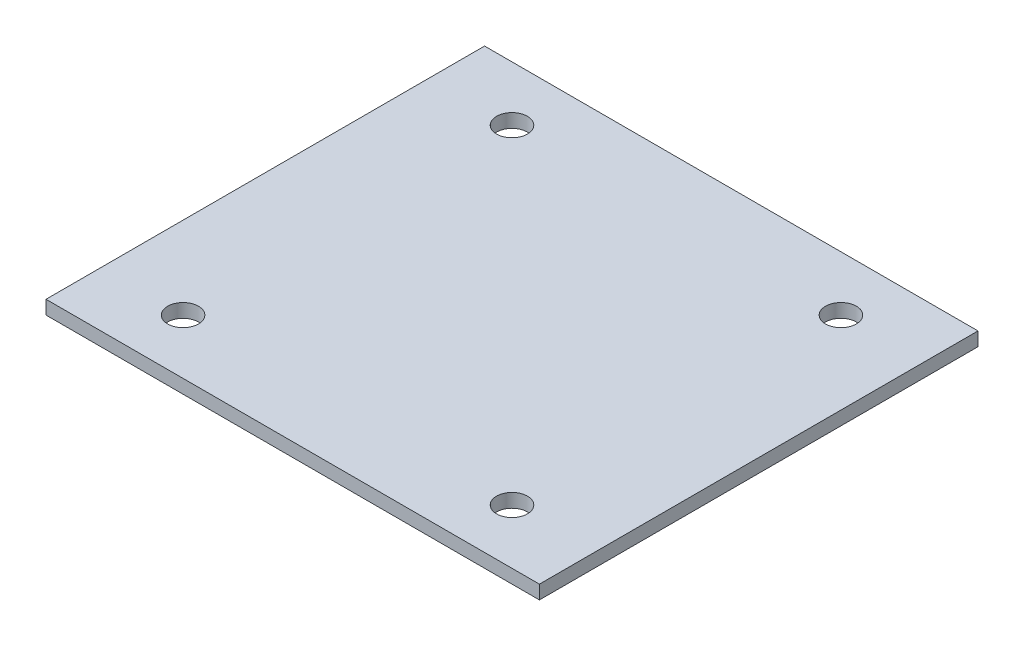
SolidWorks part; units mm, degrees
ref_plane "Front Plane" through (0, 0, 0) normal (0, 0, 1) x (1, 0, 0)
ref_plane "Top Plane" through (0, 0, 0) normal (0, 1, 0) x (1, 0, 0)
ref_plane "Right Plane" through (0, 0, 0) normal (1, 0, 0) x (0, 0, -1)
sketch "Sketch1" plane through (0, 0, 0) normal (0, 1, 0) x (1, 0, 0)
  line L1 (-57.15, 50.8) -> (57.15, 50.8)
  line L2 (-57.15, 50.8) -> (-57.15, -50.8)
  line L3 (-57.15, -50.8) -> (57.15, -50.8)
  line L4 (57.15, 50.8) -> (57.15, -50.8)
  line L5 (-57.15, 50.8) -> (57.15, -50.8) construction
  line L6 (-57.15, -50.8) -> (57.15, 50.8) construction
  point P0 (0, 0)
  dimension "D1" = 114.3
  dimension "D2" = 101.6
extrude "Boss-Extrude1" add sketch "Sketch1" along normal blind 3.175
hole_wizard "1/4 Clearance Hole1" positions "Sketch3" profile "Sketch4" hole size "1/4" standard "ANSI Inch" end condition up to next
sketch "Sketch3" plane through (0, 3.175, 0) normal (0, 1, 0) x (1, 0, 0)
  line L0 (-38.1, 50.8) -> (-38.1, 38.1) construction
  line L1 (57.15, 50.8) -> (-57.15, 50.8) construction
  line L2 (-38.1, 38.1) -> (-38.1, 12.7) construction
  line L3 (-38.1, 12.7) -> (-38.1, -12.7) construction
  line L4 (-38.1, -12.7) -> (-38.1, -38.1) construction
  line L5 (-38.1, -38.1) -> (-38.1, -50.8) construction
  line L6 (-57.15, -50.8) -> (57.15, -50.8) construction
  line L8 (-38.1, -63.5) -> (-38.1, -38.1) construction
  line L9 (-57.15, 50.8) -> (-57.15, -50.8) construction
  point P0 (-38.1, 38.1)
  point P6 (-38.1, -38.1)
  point P32 (0, 0)
  point P33 (0, 0)
  point P34 (0, 0)
  dimension "D1" = 19.05
sketch "Sketch4" plane through (-38.1, 3.175, -38.1) normal (1, 0, 0) x (0, 0, 1)
  line L0 (0, 0) -> (0, 3.175)
  line L1 (0, 3.175) -> (3.5712, 3.175)
  line L2 (3.5712, 3.175) -> (3.5712, 0)
  line L5 (3.5712, 0) -> (0, 0)
  line L11 (0, -6.35) -> (0, 107.95) construction
  dimension "Thru Hole Dia." = 7.1425
  dimension "Thru Hole Depth" = 3.175
mirror "Mirror1" about plane through (0, 0, 0) normal (1, 0, 0) of "1/4 Clearance Hole1"
